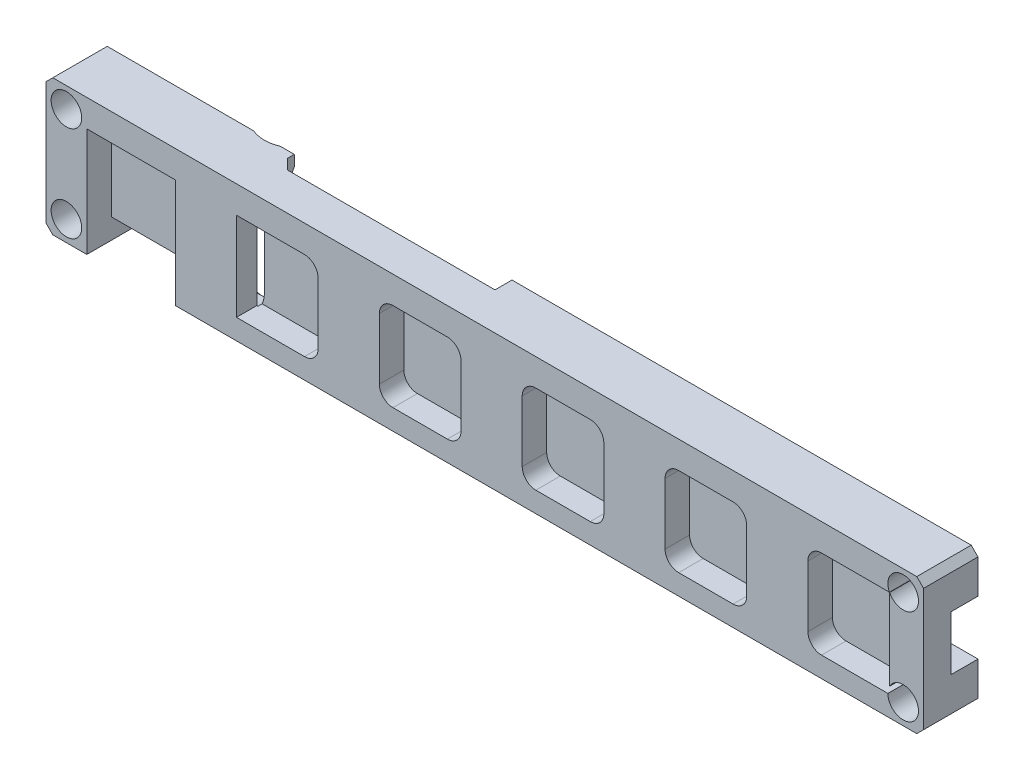
SolidWorks part; units mm, degrees
ref_plane "Front Plane" through (0, 0, 0) normal (0, 0, 1) x (1, 0, 0)
ref_plane "Top Plane" through (0, 0, 0) normal (0, 1, 0) x (1, 0, 0)
ref_plane "Right Plane" through (0, 0, 0) normal (1, 0, 0) x (0, 0, -1)
sketch "Sketch1" plane through (0, 0, 0) normal (0, 0, 1) x (1, 0, 0)
  line L1 (0, 0) -> (129, 0)
  line L2 (0, 0) -> (0, 20)
  line L3 (0, 20) -> (129, 20)
  line L4 (129, 0) -> (129, 20)
  dimension "D1" = 20
  dimension "D2" = 129
extrude "Boss-Extrude1" add sketch "Sketch1" along normal blind 8
sketch "Sketch2" plane through (0, 0, 8) normal (0, 0, 1) x (1, 0, 0)
  line L0 (0, 0) -> (0, 20) construction
  line L1 (6, 16) -> (19, 16)
  line L2 (6, 16) -> (6, 1)
  line L3 (6, 1) -> (19, 1)
  line L4 (19, 16) -> (19, 1)
  line L5 (163, 0) -> (-22, 0) construction
  line L6 (49, 3) -> (61, 3)
  line L7 (28, 16) -> (40, 16)
  line L8 (28, 16) -> (28, 3)
  line L9 (28, 3) -> (40, 3)
  line L10 (40, 16) -> (40, 3)
  line L11 (49, 16) -> (61, 16)
  line L12 (49, 16) -> (49, 3)
  line L13 (61, 16) -> (61, 3)
  line L14 (70, 3) -> (82, 3)
  line L15 (70, 16) -> (82, 16)
  line L16 (70, 16) -> (70, 3)
  line L17 (82, 16) -> (82, 3)
  line L18 (91, 3) -> (103, 3)
  line L19 (91, 16) -> (103, 16)
  line L20 (91, 16) -> (91, 3)
  line L21 (103, 16) -> (103, 3)
  line L22 (112, 3) -> (124, 3)
  line L23 (112, 16) -> (124, 16)
  line L24 (112, 16) -> (112, 3)
  line L25 (124, 16) -> (124, 3)
  circle A0 centre (126, 3) radius 2.25
  circle A1 centre (126, 17) radius 2.25
  circle A2 centre (3, 17) radius 2.25
  circle A3 centre (3, 3) radius 2.25
  point P41 (0, 0)
  dimension "D12" = 4.5
  dimension "D1" = 6
  dimension "D2" = 19
  dimension "D3" = 1
  dimension "D4" = 16
  dimension "D5" = 28
  dimension "D6" = 40
  dimension "D7" = 3
  dimension "D8" = 16
  dimension "D10" = 21
  dimension "D9" = 5
extrude "Cut-Extrude4" cut sketch "Sketch2" against normal blind 3.6 contours L25 L23 L24 L22 | L21 L19 L20 L18 | L13 L11 L12 L6 | L4 L1 L2 L3 | L10 L7 L8 L9 | L16 L14 L17 L15 region at (12.5, 8.5, 8) region at (55, 9.5, 8) region at (34, 9.5, 8) region at (97, 9.5, 8) region at (117.9934, 9.5068, 8)
extrude "Cut-Extrude7" cut sketch "Sketch2<5>" against normal through all contours L22 A0 L25 | L25 A1 L23 | A2 | A3 | L23 A1 L25 | L25 A0 L22 region at (123.8995, 3.3896, 8) region at (126.0232, 2.9957, 8) region at (126, 17, 8) region at (123.9948, 15.9897, 8) region at (3, 17, 8) region at (3, 3, 8)
sketch "Sketch2<5>" plane through (0, 0, 8) normal (0, 0, 1) x (1, 0, 0) same geometry as "Sketch2"
sketch "Sketch3" plane through (0, 0, 4.4) normal (0, 0, 1) x (1, 0, 0)
  line L0 (19, 16) -> (19, 1) construction
  line L1 (19, 3) -> (6, 3)
  line L2 (19, 3) -> (19, 0)
  line L3 (19, 0) -> (6, 0)
  line L4 (6, 3) -> (6, 0)
  line L5 (0, 0) -> (129, 0) construction
extrude "Cut-Extrude8" cut sketch "Sketch3" against normal through all both and the other way through all
sketch "Sketch4" plane through (0, 0, 0) normal (0, 0, -1) x (-1, 0, 0)
  line L0 (-24.5, 4.5961) -> (-24.5, 15.4039) construction
  line L1 (-28.5, 4.5961) -> (-28.5, 15.4039)
  line L2 (-20.5, 4.5961) -> (-20.5, 15.4039)
  line L3 (0, 10) -> (-24.5, 10) construction
  line L4 (0, 20) -> (0, 0) construction
  arc A0 (-28.5, 4.5961) -> (-20.5, 4.5961) centre (-24.5, 4.5961) ccw
  arc A1 (-20.5, 15.4039) -> (-28.5, 15.4039) centre (-24.5, 15.4039) ccw
  point P2 (-24.5, 10)
  dimension "D2" = 4
  dimension "D1" = 24.5
extrude "Cut-Extrude9" cut sketch "Sketch4" against normal blind 5
chamfer "Chamfer1" distance 1 angle 45 4 edges at (24.5, 0.5961, 0) (20.5, 10, 0) (24.5, 19.4039, 0) (28.5, 10, 0)
sketch "Sketch5" plane through (0, 0, 0) normal (0, 0, -1) x (-1, 0, 0)
  line L0 (-26.4686, 0) -> (-129, 0) construction
  line L1 (-70.5, 0) -> (-28.5, 0)
  line L2 (-70.5, 0) -> (-70.5, 20)
  line L3 (-70.5, 20) -> (-28.5, 20)
  line L4 (-28.5, 0) -> (-28.5, 20)
  line L5 (-28.5, 15.4039) -> (-28.5, 4.5961) construction
  line L6 (-129, 20) -> (-26.4686, 20) construction
  line L7 (0, 20) -> (0, 0) construction
  line L8 (0, 14) -> (-2, 14)
  line L9 (0, 14) -> (0, 6)
  line L10 (0, 6) -> (-2, 6)
  line L11 (-2, 14) -> (-2, 6)
  line L12 (-2, 10) -> (0, 10) construction
  dimension "D1" = 42
  dimension "D2" = 2
  dimension "D3" = 8
extrude "Cut-Extrude10" cut sketch "Sketch5" against normal blind 2.5
chamfer "Chamfer2" distance 1.5 angle 45 1 edges at (28.5, 17.7019, 2.5)
sketch "Sketch6" plane through (0, 0, 0) normal (0, 0, -1) x (-1, 0, 0)
  line L0 (-129, 0) -> (-129, 20) construction
  line L1 (-86, 2.5) -> (-91, 2.5)
  line L2 (-86, 2.5) -> (-86, 7)
  line L3 (-86, 7) -> (-91, 7)
  line L4 (-91, 2.5) -> (-91, 7)
  line L5 (-108, 2.5) -> (-113, 2.5)
  line L6 (-108, 2.5) -> (-108, 12.5)
  line L7 (-108, 12.5) -> (-113, 12.5)
  line L9 (-70.5, 0) -> (-129, 0) construction
  line L10 (-113, 10) -> (-129, 10) construction
  line L11 (-129, 6) -> (-113, 6)
  line L12 (-129, 6) -> (-129, 14)
  line L13 (-129, 14) -> (-113, 14)
  line L15 (-113, 2.5) -> (-113, 14)
  line L17 (-121, 6) -> (-121, 2.5)
  line L18 (-121, 2.5) -> (-113, 2.5)
  line M16 (-129, 20) -> (-129, 0)
  dimension "D1" = 86
  dimension "D2" = 5
  dimension "D3" = 2.5
  dimension "D4" = 4.5
  dimension "D5" = 21
  dimension "D6" = 5
  dimension "D7" = 2.5
  dimension "D8" = 10
  dimension "D9" = 8
extrude "Cut-Extrude11" cut sketch "Sketch6" against normal blind 4 contours L4 L1 L2 L3 | L15 L5 L6 L7 | L17 L18 L15 L11 | L15 L10 L12 L11 | L10 L15 L13 M16 region at (88.5, 4.75, 0) region at (110.5, 7.5, 0) region at (117, 4.25, 0) region at (121, 8, 0) region at (121, 12, 0)
sketch "Sketch7" plane through (0, 0, 2.5) normal (0, 0, -1) x (-1, 0, 0)
  line L5 (-70.5, 0) -> (-50.5, 0)
  line L6 (-70.5, 0) -> (-70.5, 4)
  line L7 (-70.5, 4) -> (-50.5, 4)
  line L8 (-50.5, 0) -> (-50.5, 4)
  line L9 (-70.5, 20) -> (-60.5, 20)
  line L10 (-70.5, 20) -> (-70.5, 16)
  line L11 (-70.5, 16) -> (-60.5, 16)
  line L12 (-60.5, 20) -> (-60.5, 16)
  line L13 (-41, 6) -> (-46, 6)
  line L14 (-41, 6) -> (-41, 11)
  line L15 (-41, 11) -> (-46, 11)
  line L16 (-46, 6) -> (-46, 11)
  dimension "D1" = 4
  dimension "D2" = 20
  dimension "D3" = 4
  dimension "D4" = 10
  dimension "D5" = 41
  dimension "D6" = 5
  dimension "D7" = 5
  dimension "D8" = 6
extrude "Boss-Extrude2" add sketch "Sketch7" along normal up to surface (2.5 mm away) up to face at (128.25, 17, 0)
chamfer "Chamfer3" distance 1 angle 45 2 edges at (0, 6, 1.25) (0, 14, 1.25)
fillet "Fillet1" radius 2 16 edges at (112, 16, 6.2) (112, 3, 6.2) (91, 16, 6.2) (70, 16, 6.2) (70, 3, 6.2) (91, 3, 6.2) (103, 3, 6.2) (103, 16, 6.2) (82, 16, 6.2) (82, 3, 6.2) (61, 3, 6.2) (61, 16, 6.2) (49, 16, 6.2) (49, 3, 6.2) (40, 3, 6.2) (40, 16, 6.2)
chamfer "Chamfer4" distance 1 angle 45 4 edges at (0, 20, 4) (0, 0, 4) (129, 0, 4) (129, 20, 4)
